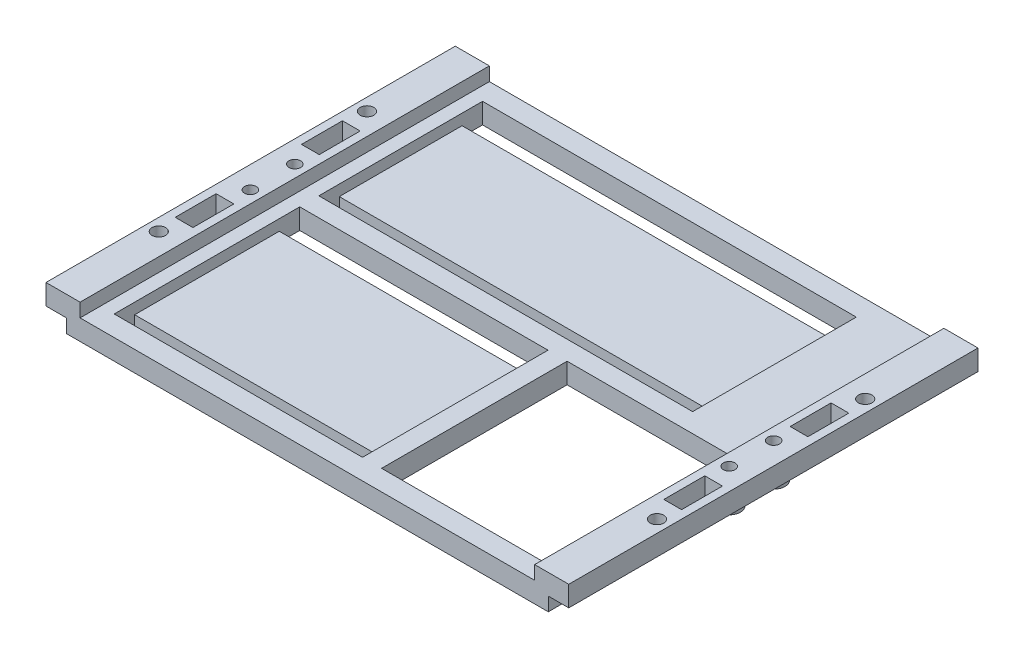
SolidWorks part; units mm, degrees
ref_plane "Front Plane" through (0, 0, 0) normal (0, 0, 1) x (1, 0, 0)
ref_plane "Top Plane" through (0, 0, 0) normal (0, 1, 0) x (1, 0, 0)
ref_plane "Right Plane" through (0, 0, 0) normal (1, 0, 0) x (0, 0, -1)
sketch "Sketch2" plane through (0, 0, 0) normal (0, 0, 1) x (1, 0, 0)
  line L0 (179.1, 12.5) -> (191.6, 12.5)
  line L1 (7.5, 0) -> (184.1, 0)
  line L2 (0, 5) -> (0, 12.5)
  line L3 (0, 12.5) -> (12.5, 12.5)
  line L4 (191.6, 5) -> (191.6, 12.5)
  line L7 (0, 5) -> (7.5, 5)
  line L8 (7.5, 0) -> (7.5, 5)
  line L11 (191.6, 5) -> (184.1, 5)
  line L12 (184.1, 0) -> (184.1, 5)
  line L14 (12.5, 12.5) -> (12.5, 7.5)
  line L15 (12.5, 7.5) -> (179.1, 7.5)
  line L16 (179.1, 12.5) -> (179.1, 7.5)
  dimension "D1" = 191.6
  dimension "D2" = 5
  dimension "D3" = 5
  dimension "D4" = 5
  dimension "D5" = 12.5
  dimension "D6" = 7.5
  dimension "D7" = 7.5
  dimension "D8" = 12.5
  dimension "D9" = 12.5
extrude "PlateFrame" add sketch "Sketch2" along normal blind 150
sketch "Sketch3" plane through (0, 12.5, 0) normal (0, 1, 0) x (1, 0, 0)
  line L0 (12.5, 0) -> (0, 0) construction
  line L2 (0, -150) -> (0, 0) construction
  line L3 (191.6, -150) -> (191.6, 0) construction
  line L4 (191.6, 0) -> (179.1, 0) construction
  circle A0 centre (8.05, -66.85) radius 2.5
  circle A1 centre (8.05, -83.15) radius 2.5
  circle A2 centre (183.55, -66.85) radius 2.5
  circle A3 centre (183.55, -83.15) radius 2.5
  dimension "D1" = 5
  dimension "D2" = 5
  dimension "D3" = 5
  dimension "D4" = 5
  dimension "D5" = 66.85
  dimension "D6" = 16.3
  dimension "D7" = 8.05
  dimension "D8" = 8.05
  dimension "D9" = 8.05
  dimension "D10" = 8.05
  dimension "D11" = 66.85
  dimension "D12" = 16.3
  dimension "D13" = 175.5
extrude "HoleSupport" cut sketch "Sketch3" against normal through all
sketch "Sketch4" plane through (0, 12.5, 0) normal (0, 1, 0) x (1, 0, 0)
  circle A0 centre (8.05, -66.85) radius 2.15
  circle A1 centre (8.05, -83.15) radius 2.15
  circle A2 centre (183.55, -83.15) radius 2.15
  circle A3 centre (183.55, -66.85) radius 2.15
  circle A4 centre (183.55, -66.85) radius 4.15
  circle A5 centre (183.55, -83.15) radius 4.15
  circle A6 centre (8.05, -66.85) radius 4.15
  circle A7 centre (8.05, -83.15) radius 4.15
  dimension "D1" = 2
extrude "CylindricalSupports" add sketch "Sketch4" against normal blind 12.5
sketch "Sketch8" plane through (0, 7.5, 0) normal (0, 1, 0) x (1, 0, 0)
  line L0 (12.5, -150) -> (12.5, 0) construction
  line L2 (154.5, -7.5) -> (17.5, -7.5)
  line L3 (154.5, -7.5) -> (154.5, -67.5)
  line L4 (154.5, -67.5) -> (17.5, -67.5)
  line L5 (17.5, -7.5) -> (17.5, -67.5)
  line L6 (108.5, -142.5) -> (17.5, -142.5)
  line L7 (108.5, -142.5) -> (108.5, -74.5)
  line L8 (108.5, -74.5) -> (17.5, -74.5)
  line L9 (17.5, -142.5) -> (17.5, -74.5)
  line L10 (179.1, 0) -> (12.5, 0) construction
  line L11 (179.1, -150) -> (12.5, -150) construction
  dimension "D1" = 5
  dimension "D2" = 7.5
  dimension "D3" = 7.5
  dimension "D4" = 5
  dimension "D5" = 60
  dimension "D6" = 68
  dimension "D7" = 137
  dimension "D8" = 91
extrude "ItemLayout" cut sketch "Sketch8" against normal blind 4
sketch "Sketch9" plane through (0, 7.5, 0) normal (0, 1, 0) x (1, 0, 0)
  line L0 (179.1, -150) -> (179.1, 0) construction
  line L1 (115.5, -74.5) -> (174.1, -74.5)
  line L2 (115.5, -74.5) -> (115.5, -142.5)
  line L3 (115.5, -142.5) -> (174.1, -142.5)
  line L4 (174.1, -74.5) -> (174.1, -142.5)
  line L5 (179.1, -150) -> (12.5, -150) construction
  line L7 (108.5, -142.5) -> (108.5, -74.5) construction
  dimension "D1" = 5
  dimension "D2" = 7.5
  dimension "D3" = 68
  dimension "D4" = 7
extrude "HoleCutout" cut sketch "Sketch9" against normal blind 7.5
sketch "Sketch10" plane through (0, 3.5, 0) normal (0, 1, 0) x (1, 0, 0)
  line L0 (108.5, -142.5) -> (108.5, -74.5) construction
  line L1 (17.5, -74.5) -> (108.5, -74.5)
  line L2 (17.5, -74.5) -> (17.5, -82)
  line L3 (17.5, -82) -> (108.5, -82)
  line L4 (108.5, -74.5) -> (108.5, -82)
  line L5 (108.5, -142.5) -> (108.5, -74.5) construction
  line L6 (17.5, -142.5) -> (108.5, -142.5)
  line L7 (17.5, -142.5) -> (17.5, -135)
  line L8 (17.5, -135) -> (108.5, -135)
  line L9 (108.5, -142.5) -> (108.5, -135)
  line L10 (154.5, -67.5) -> (154.5, -7.5) construction
  line L11 (17.5, -7.5) -> (154.5, -7.5)
  line L12 (17.5, -7.5) -> (17.5, -15)
  line L13 (17.5, -15) -> (154.5, -15)
  line L14 (154.5, -7.5) -> (154.5, -15)
  line L16 (17.5, -67.5) -> (154.5, -67.5)
  line L17 (17.5, -67.5) -> (17.5, -60)
  line L18 (17.5, -60) -> (154.5, -60)
  line L19 (154.5, -67.5) -> (154.5, -60)
  dimension "D1" = 7.5
  dimension "D2" = 7.5
  dimension "D3" = 7.5
  dimension "D4" = 7.5
extrude "VelcroCut" cut sketch "Sketch10" against normal blind 3.5
sketch "Sketch11" plane through (0, 12.5, 0) normal (0, 1, 0) x (1, 0, 0)
  line L0 (12.5, -150) -> (12.5, 0) construction
  line L1 (9.5, -59.35) -> (3, -59.35)
  line L2 (9.5, -59.35) -> (9.5, -44.35)
  line L3 (9.5, -44.35) -> (3, -44.35)
  line L4 (3, -59.35) -> (3, -44.35)
  line L5 (188.6, -59.35) -> (182.1, -59.35)
  line L6 (188.6, -59.35) -> (188.6, -44.35)
  line L7 (188.6, -44.35) -> (182.1, -44.35)
  line L8 (182.1, -59.35) -> (182.1, -44.35)
  line L9 (182.1, -90.65) -> (188.6, -90.65)
  line L10 (182.1, -90.65) -> (182.1, -105.65)
  line L11 (182.1, -105.65) -> (188.6, -105.65)
  line L12 (188.6, -90.65) -> (188.6, -105.65)
  line L13 (3, -90.65) -> (9.5, -90.65)
  line L14 (3, -90.65) -> (3, -105.65)
  line L15 (3, -105.65) -> (9.5, -105.65)
  line L16 (9.5, -90.65) -> (9.5, -105.65)
  line L17 (12.5, -150) -> (12.5, 0) construction
  line L18 (179.1, -150) -> (179.1, 0) construction
  line L19 (179.1, -150) -> (179.1, 0) construction
  circle A4 centre (8.05, -66.85) radius 2.15 construction
  circle A5 centre (8.05, -83.15) radius 2.15 construction
  circle A6 centre (183.55, -66.85) radius 2.15 construction
  circle A7 centre (183.55, -83.15) radius 2.15 construction
  dimension "D2" = 7.5
  dimension "D12" = 7.5
  dimension "D11" = 7.5
  dimension "D17" = 7.5
  dimension "D3" = 3
  dimension "D4" = 3
  dimension "D5" = 6.5
  dimension "D6" = 15
  dimension "D7" = 6.5
  dimension "D8" = 15
  dimension "D9" = 3
  dimension "D10" = 3
  dimension "D13" = 15
  dimension "D14" = 15
  dimension "D15" = 6.5
  dimension "D16" = 6.5
extrude "CutShellHoles" cut sketch "Sketch11" against normal blind 12.5
sketch "Sketch12" plane through (0, 12.5, 0) normal (0, 1, 0) x (1, 0, 0)
  line L0 (12.5, -150) -> (12.5, 0) construction
  line L1 (12.5, -150) -> (12.5, 0) construction
  line L2 (179.1, -150) -> (179.1, 0) construction
  line L3 (179.1, -150) -> (179.1, 0) construction
  circle A0 centre (4.5, -36.85) radius 2.5
  circle A1 centre (4.5, -113.15) radius 2.5
  circle A2 centre (187.1, -36.85) radius 2.5
  circle A3 centre (187.1, -113.15) radius 2.5
  circle A4 centre (8.05, -66.85) radius 2.15 construction
  circle A5 centre (8.05, -83.15) radius 2.15 construction
  circle A6 centre (183.55, -66.85) radius 2.15 construction
  circle A7 centre (183.55, -83.15) radius 2.15 construction
  dimension "D1" = 30
  dimension "D2" = 30
  dimension "D3" = 30
  dimension "D4" = 30
  dimension "D5" = 8
  dimension "D6" = 5
  dimension "D7" = 5
  dimension "D8" = 8
  dimension "D9" = 5
  dimension "D10" = 5
  dimension "D11" = 8
  dimension "D12" = 8
extrude "StandoffHoles" cut sketch "Sketch12" against normal through all
